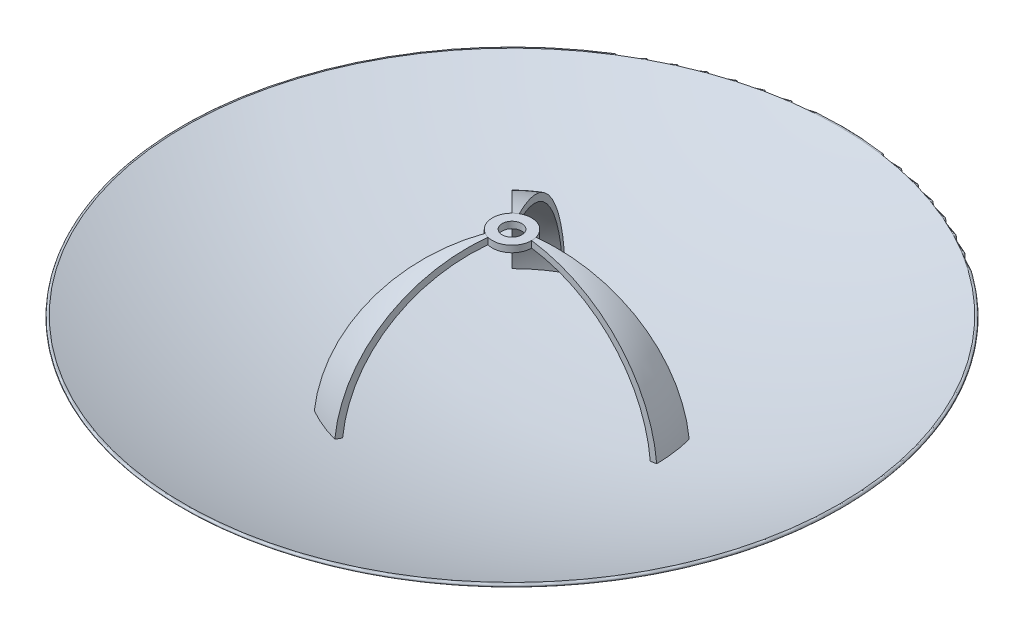
SolidWorks part; units mm, degrees
material "Alumina"
ref_plane "Front Plane" through (0, 0, 0) normal (0, 0, 1) x (1, 0, 0)
ref_plane "Top Plane" through (0, 0, 0) normal (0, 1, 0) x (1, 0, 0)
ref_plane "Right Plane" through (0, 0, 0) normal (1, 0, 0) x (0, 0, -1)
sketch "Sketch1" plane through (0, 0, 0) normal (0, 0, 1) x (1, 0, 0)
  line L0 (0, 0) -> (0, 1231.1708) construction
  line L1 (-500, 106.1012) -> (500, 106.1012) construction
  line L2 (500, 106.1012) -> (502.0306, 101.5321) construction
  line L3 (0, 0) -> (0, -11.0743) construction
  line L4 (0, -5) -> (0, 0)
  arc A0 (0, 0) -> (500, 106.1012) centre (0, 1231.1708) ccw
  arc A1 (0, -5) -> (502.0306, 101.5321) centre (0, 1231.1708) ccw
  arc A2 (502.0306, 101.5321) -> (500, 106.1012) centre (501.0153, 103.8167) ccw
  arc A4 (-500, 106.1012) -> (500, 106.1012) centre (0, 1231.1708) ccw construction
  arc A5 (-502.0306, 101.5321) -> (502.0306, 101.5321) centre (0, 1231.1708) ccw construction
  dimension "D1" = 5
  dimension "D2" = 1000
revolve "Revolve1" add sketch "Sketch1" angle 360 about L0
sketch "Sketch2" plane through (0, 0, 0) normal (0, 1, 0) x (1, 0, 0)
  circle A0 centre (0, 0) radius 20
  circle A1 centre (0, 0) radius 15
  dimension "D1" = 40
  dimension "D2" = 5
extrude "Boss-Extrude1" add sketch "Sketch2" along normal blind 0.0001 and the other way blind 50
sketch "Sketch3" plane through (0, 0, 0) normal (1, 0, 0) x (0, 0, -1)
  line L0 (-20, -50) -> (20, -50) construction
  line L1 (20, -50) -> (20, -4.8382) construction
  circle A0 centre (0, -35) radius 3
  dimension "D3" = 6
  dimension "D1" = 15
  dimension "D2" = 20
extrude "Cut-Extrude1" cut sketch "Sketch3" against normal through all both and the other way through all
ref_plane "Plane1" through (0, 210, 0) normal (0, 1, 0) x (1, 0, 0)
sketch "Sketch8" plane through (0, 210, 0) normal (0, 1, 0) x (1, 0, 0)
  circle A0 centre (0, 0) radius 30
extrude "Boss-Extrude6" add sketch "Sketch8" along normal blind 10 separate body
sketch "Sketch9" plane through (0, 0, 0) normal (0, 0, 1) x (1, 0, 0)
  line L0 (553.8668, 210) -> (-553.8668, 210) construction
  line L1 (30, 220) -> (30, 210)
  line L2 (211.3434, 18.2753) -> (221.1315, 20.0216)
  arc A0 (30, 220) -> (221.1315, 20.0216) centre (0, 0) cw
  arc A1 (0, 0) -> (500, 106.1012) centre (0, 1231.1708) ccw construction
  arc A2 (30, 210) -> (211.3434, 18.2753) centre (0, 0) cw
revolve "Revolve6" add sketch "Sketch9" angle 15 about L0
pattern_circular "CirPattern2" count 3 over 360 about axis through (0, 0, 0) along (0, 1, 0) of "Revolve6"
sketch "Sketch10" plane through (0, 220, 0) normal (0, 1, 0) x (1, 0, 0)
  circle A0 centre (0, 0) radius 15
extrude "Cut-Extrude2" cut sketch "Sketch10" against normal blind 10
